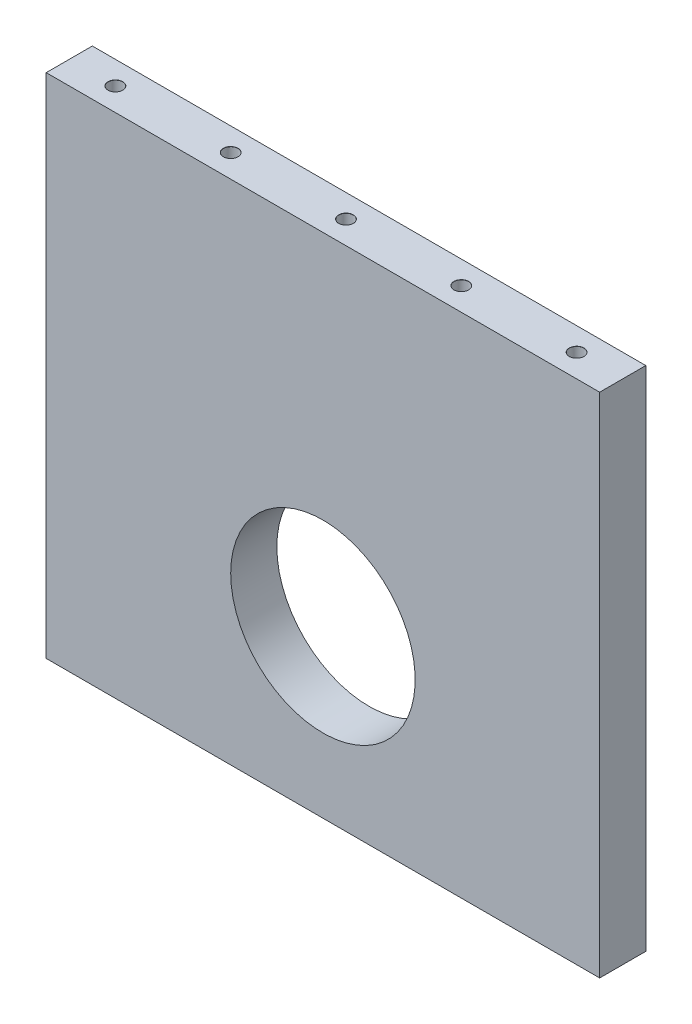
SolidWorks part; units mm, degrees
material "6061-T6 (SS)"
ref_plane "Front Plane" through (0, 0, 0) normal (0, 0, 1) x (1, 0, 0)
ref_plane "Top Plane" through (0, 0, 0) normal (0, 1, 0) x (1, 0, 0)
ref_plane "Right Plane" through (0, 0, 0) normal (1, 0, 0) x (0, 0, -1)
sketch "Sketch1" plane through (0, 0, 0) normal (0, 0, 1) x (1, 0, 0)
  line L1 (0, 0) -> (120, 0)
  line L2 (0, 0) -> (0, 110)
  line L3 (0, 110) -> (120, 110)
  line L4 (120, 0) -> (120, 110)
  dimension "D1" = 110
  dimension "D2" = 120
extrude "Boss-Extrude1" add sketch "Sketch1" along normal blind 10
sketch "Sketch2" plane through (0, 110, 0) normal (0, 1, 0) x (1, 0, 0)
  line L0 (0, -5) -> (120, -5) construction
  line L1 (0, -10) -> (0, 0) construction
  line L2 (120, -10) -> (120, 0) construction
  point P9 (60, -5)
  point P18 (85, -5)
  point P19 (110, -5)
  point P20 (60, -5)
  point P21 (85, -5)
  point P22 (35, -5)
  point P23 (60, -5)
  point P24 (35, -5)
  point P25 (10, -5)
  dimension "D1" = 3
  dimension "D2" = 3
hole_wizard "Tap Drill for M3 Helicoil1" positions "Sketch2" profile "Sketch4" hole size "M3x0.5" standard "DIN"
sketch "Sketch4" plane through (10, 110, 5) normal (1, 0, 0) x (0, 0, 1)
  line L0 (0, 0) -> (0, 6.9464)
  line L1 (0, 6.9464) -> (1.575, 6)
  line L2 (1.575, 6) -> (1.575, 0.025)
  line L3 (1.575, 0.025) -> (1.6, 0)
  line L5 (1.6, 0) -> (0, 0)
  line L6 (-1.575, 0.025) -> (-1.6, 0) construction
  line L10 (0, 6.9464) -> (-1.575, 6) construction
  line L11 (0, -6.35) -> (0, 107.95) construction
  dimension "Hole Dia." = 3.15
  dimension "Hole Depth" = 6
  dimension "Near C'Sink Dia." = 3.2
  dimension "Near C'Sink Angle" = 90
  dimension "Drill Angle" = 118
sketch "Sketch5" plane through (0, 0, 0) normal (0, 0, -1) x (-1, 0, 0)
  line L0 (-120, 110) -> (0, 110) construction
  point P8 (-60, 36)
  point P11 (-60, 45.6578)
  point P14 (0, 0)
  dimension "D1" = 74
hole_wizard "Ø40.0 (40) Diameter Hole1" positions "Sketch5" profile "Sketch7" hole size "Ø40.0" standard "DIN" end condition through all
sketch "Sketch7" plane through (60, 36, 0) normal (1, 0, 0) x (0, 1, 0)
  line L0 (0, 0) -> (0, 10)
  line L1 (0, 10) -> (20, 10)
  line L2 (20, 10) -> (20, 0)
  line L5 (20, 0) -> (0, 0)
  line L11 (0, -6.35) -> (0, 107.95) construction
  dimension "Thru Hole Dia." = 40
  dimension "Thru Hole Depth" = 10
